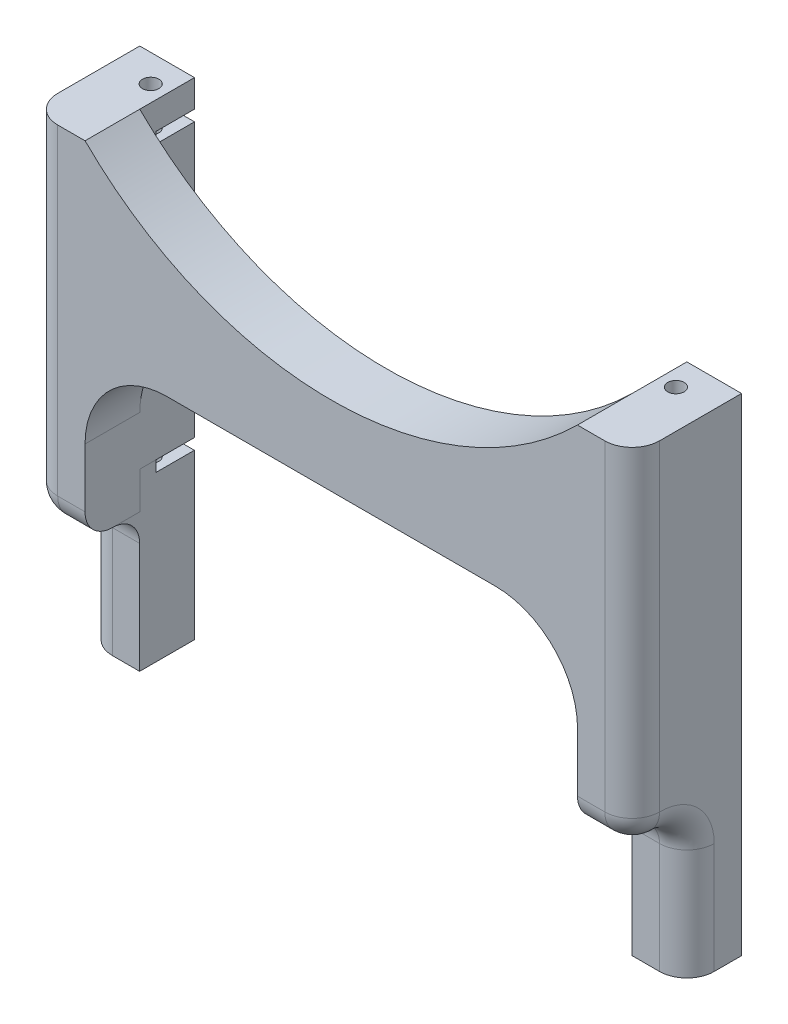
SolidWorks part; units mm, degrees
ref_plane "Front Plane" through (0, 0, 0) normal (0, 0, 1) x (1, 0, 0)
ref_plane "Top Plane" through (0, 0, 0) normal (0, 1, 0) x (1, 0, 0)
ref_plane "Right Plane" through (0, 0, 0) normal (1, 0, 0) x (0, 0, -1)
sketch "Sketch1" plane through (0, 0, 0) normal (0, 0, 1) x (1, 0, 0)
  line L1 (50, -25) -> (-50, -25)
  line L2 (50, -25) -> (50, 25)
  line L3 (50, 25) -> (-50, 25)
  line L4 (-50, -25) -> (-50, 25)
  line L5 (50, -25) -> (-50, 25) construction
  line L6 (50, 25) -> (-50, -25) construction
  arc A0 (-45, 25) -> (45, 25) centre (0, 76.0588) ccw
  arc A1 (-45.0185, -25) -> (45.0185, -25) centre (0, -76.1077) cw
  point P0 (0, 0)
  point P6 (-45, 25)
  point P7 (-45.0185, -25)
  point P8 (45, 25)
  point P9 (45.0185, -25)
  point P16 (0, -8)
  point P17 (0, 8)
  dimension "D1" = 50
  dimension "D2" = 100
  dimension "D3" = 5
  dimension "D4" = 5
  dimension "D5" = 8
  dimension "D6" = 8
extrude "Boss-Extrude1" add sketch "Sketch1" along normal blind 10 contours L1 A1 L2 L3 A0 L4 region at (0, 0.0026, 0)
sketch "Sketch2" plane through (0, 25, 0) normal (0, 1, 0) x (1, 0, 0)
  line L0 (-50, -5) -> (50, -5) construction
  line L1 (-50, -10) -> (-50, 0) construction
  line L2 (50, -10) -> (50, 0) construction
  line L3 (-45, -10) -> (-45, 0) construction
  circle A0 centre (-48, -5) radius 1.5
  circle A1 centre (48, -5) radius 1.5
  point P7 (-48, -5)
  point P11 (48, -5)
  dimension "D2" = 96
  dimension "D3" = 3
extrude "Cut-Extrude1" cut sketch "Sketch2" against normal through all both and the other way through all
sketch "Sketch9" plane through (50, 0, 0) normal (1, 0, 0) x (0, 0, -1)
  line L1 (0, 25) -> (-10, 25)
  line L2 (0, 25) -> (0, -25)
  line L3 (0, -25) -> (-10, -25)
  line L4 (-10, 25) -> (-10, -25)
extrude "Boss-Extrude9" add sketch "Sketch9" along normal blind 5
sketch "Sketch10" plane through (-50, 0, 0) normal (-1, 0, 0) x (0, 0, 1)
  line L1 (10, -25) -> (0, -25)
  line L2 (10, -25) -> (10, 25)
  line L3 (10, 25) -> (0, 25)
  line L4 (0, -25) -> (0, 25)
extrude "Boss-Extrude10" add sketch "Sketch10" along normal blind 5
sketch "Sketch11" plane through (0, 25, 0) normal (0, 1, 0) x (1, 0, 0)
  line L0 (50, 0) -> (50, -7)
  line L1 (55, 0) -> (45, 0) construction
  line L2 (-50, 0) -> (-50, -7)
  line L3 (-45, 0) -> (-55, 0) construction
  line L4 (50, -7) -> (45, -7)
  line L5 (45, -10) -> (45, 0) construction
  line L6 (-50, -7) -> (-45, -7)
  line L7 (-45, -10) -> (-45, 0) construction
  line L8 (50, 0) -> (55, 0)
  line L9 (55, 0) -> (55, -10)
  line L10 (55, -10) -> (45, -10)
  line L11 (45, -10) -> (45, -7)
  line L12 (-45, -7) -> (-45, -10)
  line L13 (-45, -10) -> (-55, -10)
  line L14 (-55, -10) -> (-55, 0)
  line L15 (-55, 0) -> (-50, 0)
  circle A1 centre (48, -5) radius 1.5 construction
  circle A2 centre (-48, -5) radius 1.5 construction
  dimension "D1" = 100
  dimension "D2" = 2
  dimension "D3" = 2
extrude "Boss-Extrude11" add sketch "Sketch11" along normal blind 2
sketch "Sketch12" plane through (0, 27, 0) normal (0, 1, 0) x (1, 0, 0)
  line L0 (45, -7) -> (45, -10) construction
  line L1 (55, -10) -> (45, -10)
  line L2 (55, -10) -> (55, 0)
  line L3 (55, 0) -> (45, 0)
  line L4 (45, -10) -> (45, 0)
  line L6 (-55, -10) -> (-45, -10)
  line L7 (-55, -10) -> (-55, 0)
  line L8 (-55, 0) -> (-45, 0)
  line L9 (-45, -10) -> (-45, 0)
  dimension "D1" = 0
extrude "Boss-Extrude12" add sketch "Sketch12" along normal blind 5
sketch "Sketch13" plane through (0, 25, 0) normal (0, 1, 0) x (1, 0, 0)
  circle A0 centre (48, -5) radius 1.5
  circle A1 centre (-48, -5) radius 1.5
extrude "Cut-Extrude2" cut sketch "Sketch13" along normal up to surface (7 mm away) up to face at (-50, 32, 5)
sketch "Sketch14" plane through (0, -25, 0) normal (0, -1, 0) x (1, 0, 0)
  line L0 (50.0092, 0) -> (50.0092, 7)
  line L1 (55, 0) -> (45.0185, 0) construction
  line L2 (50.0092, 7) -> (45.0185, 7)
  line L3 (45.0185, 10) -> (45.0185, 0) construction
  line L4 (-50.0092, 0) -> (-50.0092, 7)
  line L5 (-45.0185, 0) -> (-55, 0) construction
  line L6 (-50.0092, 7) -> (-45.0185, 7)
  line L7 (-45.0185, 10) -> (-45.0185, 0) construction
  line L8 (-45.0185, 7) -> (-45.0185, 10)
  line L9 (-45.0185, 10) -> (-55, 10)
  line L10 (-55, 10) -> (-55, 0)
  line L11 (-55, 0) -> (-50.0092, 0)
  line L12 (45.0185, 7) -> (45.0185, 10)
  line L13 (45.0185, 10) -> (55, 10)
  line L14 (55, 10) -> (55, 0)
  line L15 (55, 0) -> (50.0092, 0)
  circle A0 centre (48, 5) radius 1.5 construction
  dimension "D1" = 2
extrude "Boss-Extrude13" add sketch "Sketch14" along normal blind 2
sketch "Sketch15" plane through (0, -27, 0) normal (0, -1, 0) x (1, 0, 0)
  line L1 (-55, 0) -> (-45.0185, 0)
  line L2 (-55, 0) -> (-55, 10)
  line L3 (-55, 10) -> (-45.0185, 10)
  line L4 (-45.0185, 0) -> (-45.0185, 10)
  line L5 (55, 10) -> (45.0185, 10)
  line L6 (55, 10) -> (55, 0)
  line L7 (55, 0) -> (45.0185, 0)
  line L8 (45.0185, 10) -> (45.0185, 0)
extrude "Boss-Extrude14" add sketch "Sketch15" along normal blind 30
sketch "Sketch16" plane through (0, -25, 0) normal (0, -1, 0) x (1, 0, 0)
  circle A1 centre (48, 5) radius 1.5
  circle A3 centre (-48, 5) radius 1.5
extrude "Cut-Extrude3" cut sketch "Sketch16" along normal up to surface (32 mm away) up to face at (-50.0092, -57, 5)
sketch "Sketch17" plane through (0, 0, 10) normal (0, 0, 1) x (1, 0, 0)
  line L0 (55, 32) -> (55, -57) construction
  line L1 (-55, 32) -> (55, 32)
  line L2 (-55, 32) -> (-55, -31.7396)
  line L3 (-55, -31.7396) -> (55, -31.7396)
  line L4 (55, 32) -> (55, -31.7396)
extrude "Boss-Extrude15" add sketch "Sketch17" along normal blind 10
sketch "Sketch18" plane through (0, 0, 0) normal (0, 0, -1) x (-1, 0, 0)
  line L0 (50, 25) -> (50.0092, -25) construction
  line L1 (50.0046, -1) -> (-50.0092, -1)
  line L2 (50.0046, -1) -> (50.0046, 1)
  line L3 (50.0046, 1) -> (-50.0092, 1)
  line L4 (-50.0092, -1) -> (-50.0092, 1)
  point P0 (-50, 25)
  point P1 (-50.0092, -25)
  point P3 (-50.0092, 0)
  point P5 (45, 25)
  point P6 (45.0185, -25)
  point P8 (50.0046, 0)
  point P10 (-50.0092, 1)
  point P11 (50.0046, 0)
  point P13 (50.0046, -1)
  dimension "D1" = 1
  dimension "D2" = 1
extrude "Cut-Extrude4" cut sketch "Sketch18" against normal up to surface (7 mm away) up to face at (47.5, 26, 7)
sketch "Sketch19" plane through (0, 0, 0) normal (0, 0, -1) x (-1, 0, 0)
  line L1 (45, 25) -> (-45.0185, 25)
  line L2 (45, 25) -> (45, -25)
  line L3 (45, -25) -> (-45.0185, -25)
  line L4 (-45.0185, 25) -> (-45.0185, -25)
extrude "Cut-Extrude5" cut sketch "Sketch19" against normal up to surface (10 mm away) up to face at (0, 24.25, 10)
sketch "Sketch20" plane through (0, 0, 10) normal (0, 0, -1) x (-1, 0, 0)
  line L0 (-45, 32) -> (45, 32) construction
  line L1 (-45, 32) -> (-45, 25) construction
  line L2 (-45, 32) -> (45, 32)
  arc A0 (-45, 32) -> (45, 32) centre (0, 77.3143) ccw
extrude "Cut-Extrude6" cut sketch "Sketch20" against normal through all
sketch "Sketch21" plane through (0, 0, 10) normal (0, 0, -1) x (-1, 0, 0)
  line L1 (-45.0185, -31.7396) -> (45, -31.7396)
  line L2 (-45.0185, -31.7396) -> (-45.0185, -1)
  line L3 (-45.0185, -1) -> (45, -1)
  line L4 (45, -31.7396) -> (45, -1)
extrude "Cut-Extrude7" cut sketch "Sketch21" against normal through all
fillet "Fillet1" radius 5 4 edges at (50.0092, -31.7396, 20) (50.0092, -31.7396, 10) (-50, -31.7396, 20) (-50.0092, -31.7396, 10)
fillet "Fillet2" radius 15 2 edges at (45.0185, -1, 15) (-45, -1, 15)
fillet "Fillet3" radius 5 8 edges at (55, -46.8698, 10) (55, -33.2041, 11.4645) (55, -30.2752, 18.5355) (-55, -46.8698, 10) (-55, -33.2041, 11.4645) (-55, -30.2752, 18.5355) (55, 2.6302, 20) (-55, 2.6302, 20)
